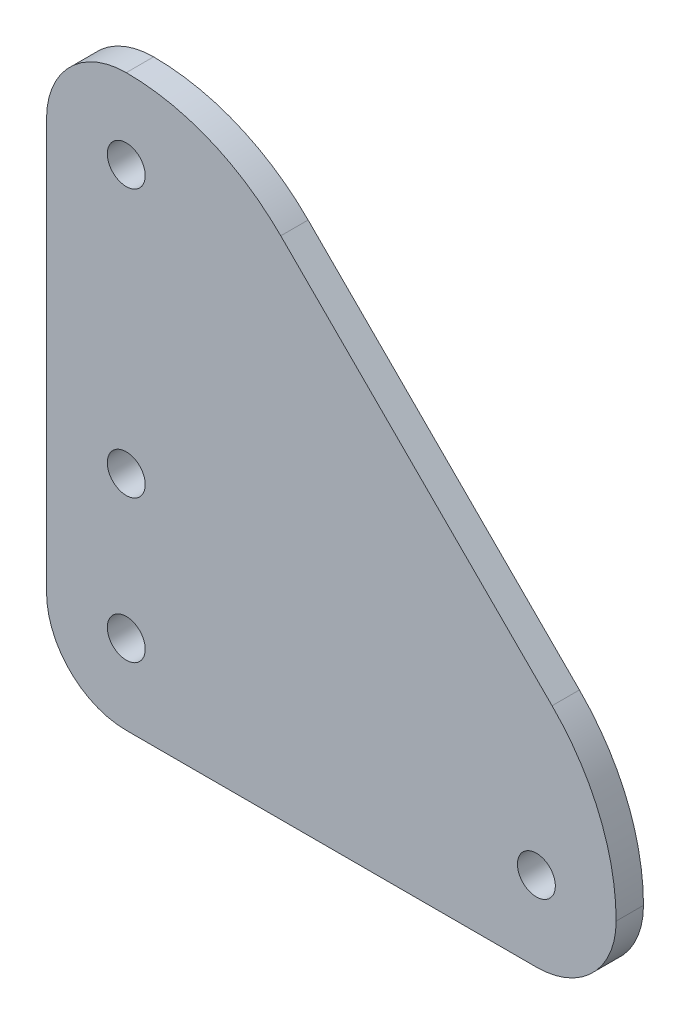
SolidWorks part; units mm, degrees
material "PET"
ref_plane "Front Plane" through (0, 0, 0) normal (0, 0, 1) x (1, 0, 0)
ref_plane "Top Plane" through (0, 0, 0) normal (0, 1, 0) x (1, 0, 0)
ref_plane "Right Plane" through (0, 0, 0) normal (1, 0, 0) x (0, 0, -1)
sketch "Sketch1" plane through (0, 0, 0) normal (0, 0, 1) x (1, 0, 0)
  line L0 (0, 0) -> (0, 133)
  line L1 (21.5, 21.5) -> (66.5, 21.5) construction
  line L2 (66.5, 21.5) -> (111.5, 21.5) construction
  line L3 (21.5, 21.5) -> (21.5, 52.7884) construction
  line L4 (43, 133) -> (0, 133)
  line L5 (133, 0) -> (0, 0)
  line L6 (21.5, 52.7884) -> (21.5, 84.0768) construction
  line L7 (133, 43) -> (133, 0)
  line L8 (43, 133) -> (133, 43)
  line L9 (133, 21.5) -> (111.5, 21.5) construction
  line L10 (21.5, 133) -> (21.5, 84.0768) construction
  circle A0 centre (21.5, 21.5) radius 4.1188 construction
  circle A1 centre (21.5, 111.5) radius 4.1187 construction
  circle A2 centre (111.5, 21.5) radius 4.1188 construction
  circle A3 centre (21.5, 52.7884) radius 4.1188 construction
  dimension "D1" = 90
  dimension "E" = 8.2375
  dimension "D2" = 21.5
  dimension "C" = 133
  dimension "D3" = 31.2884
  dimension "B" = 133
  dimension "D4" = 21.5
  dimension "D5" = 21.5
extrude "Boss-Extrude1" add sketch "Sketch1" along normal mid plane 6
fillet "Fillet1" radius 21.5 3 edges at (133, 0, 0) (0, 0, 0) (0, 133, 0)
fillet "Fillet2" radius 52 2 edges at (133, 43, 0) (43, 133, 0)
sketch "Sketch3" plane through (0, 0, 3) normal (0, 0, 1) x (1, 0, 0)
  line L6 (114.9411, 55.402) -> (55.402, 114.9411)
  line L7 (4, 111.5) -> (4, 21.5)
  line L8 (21.5, 4) -> (111.5, 4)
  line L9 (114.9411, 55.402) -> (55.402, 114.9411)
  line L10 (4, 111.5) -> (4, 21.5)
  line L11 (21.5, 4) -> (111.5, 4)
  line L12 (117.7696, 58.2304) -> (58.2304, 117.7696)
  line L13 (0, 111.5) -> (0, 21.5)
  line L14 (21.5, 0) -> (111.5, 0)
  line L15 (117.7696, 58.2304) -> (58.2304, 117.7696)
  line L16 (0, 111.5) -> (0, 21.5)
  line L17 (21.5, 0) -> (111.5, 0)
  arc A10 (111.5, 4) -> (129, 21.4985) centre (111.5, 21.5) ccw
  arc A11 (129, 21.4985) -> (114.9411, 55.402) centre (81, 21.4609) ccw
  arc A12 (55.402, 114.9411) -> (21.4985, 129) centre (21.4609, 81) ccw
  arc A13 (21.4985, 129) -> (4, 111.5) centre (21.5, 111.5) ccw
  arc A14 (4, 21.5) -> (21.5, 4) centre (21.5, 21.5) ccw
  arc A15 (111.5, 4) -> (129, 21.4985) centre (111.5, 21.5) ccw
  arc A16 (129, 21.4985) -> (114.9411, 55.402) centre (81, 21.4609) ccw
  arc A17 (55.402, 114.9411) -> (21.4985, 129) centre (21.4609, 81) ccw
  arc A18 (21.4985, 129) -> (4, 111.5) centre (21.5, 111.5) ccw
  arc A19 (4, 21.5) -> (21.5, 4) centre (21.5, 21.5) ccw
  arc A20 (111.5, 0) -> (133, 21.5) centre (111.5, 21.5) ccw
  arc A21 (133, 21.5) -> (117.7696, 58.2304) centre (81, 21.4609) ccw
  arc A22 (58.2304, 117.7696) -> (21.5, 133) centre (21.4609, 81) ccw
  arc A23 (21.5, 133) -> (0, 111.5) centre (21.5, 111.5) ccw
  arc A24 (0, 21.5) -> (21.5, 0) centre (21.5, 21.5) ccw
  arc A25 (111.5, 0) -> (133, 21.5) centre (111.5, 21.5) ccw
  arc A26 (133, 21.5) -> (117.7696, 58.2304) centre (81, 21.4609) ccw
  arc A27 (58.2304, 117.7696) -> (21.5, 133) centre (21.4609, 81) ccw
  arc A28 (21.5, 133) -> (0, 111.5) centre (21.5, 111.5) ccw
  arc A29 (0, 21.5) -> (21.5, 0) centre (21.5, 21.5) ccw
  dimension "D1" = 4
  dimension "D2" = 0
extrude "Cut-Extrude1" cut sketch "Sketch3" against normal through all body kept at (129, 21.4985, -3)
hole_wizard "5/16 Clearance Hole1" positions "Sketch6" profile "Sketch5" hole size "5/16" standard "ANSI Inch" end condition through all
sketch "Sketch6" plane through (0, 0, 3) normal (0, 0, 1) x (1, 0, 0)
  point P0 (21.5, 111.5)
  point P3 (21.5, 52.7884)
  point P6 (21.5, 21.5)
  point P9 (111.5, 21.5)
sketch "Sketch5" plane through (21.5, 111.5, 3) normal (1, 0, 0) x (0, -1, 0)
  line L0 (0, 0) -> (0, 6)
  line L1 (0, 6) -> (4.1592, 6)
  line L2 (4.1592, 6) -> (4.1592, 0)
  line L5 (4.1592, 0) -> (0, 0)
  line L11 (0, -6.35) -> (0, 107.95) construction
  dimension "Thru Hole Dia." = 8.3185
  dimension "Thru Hole Depth" = 6
